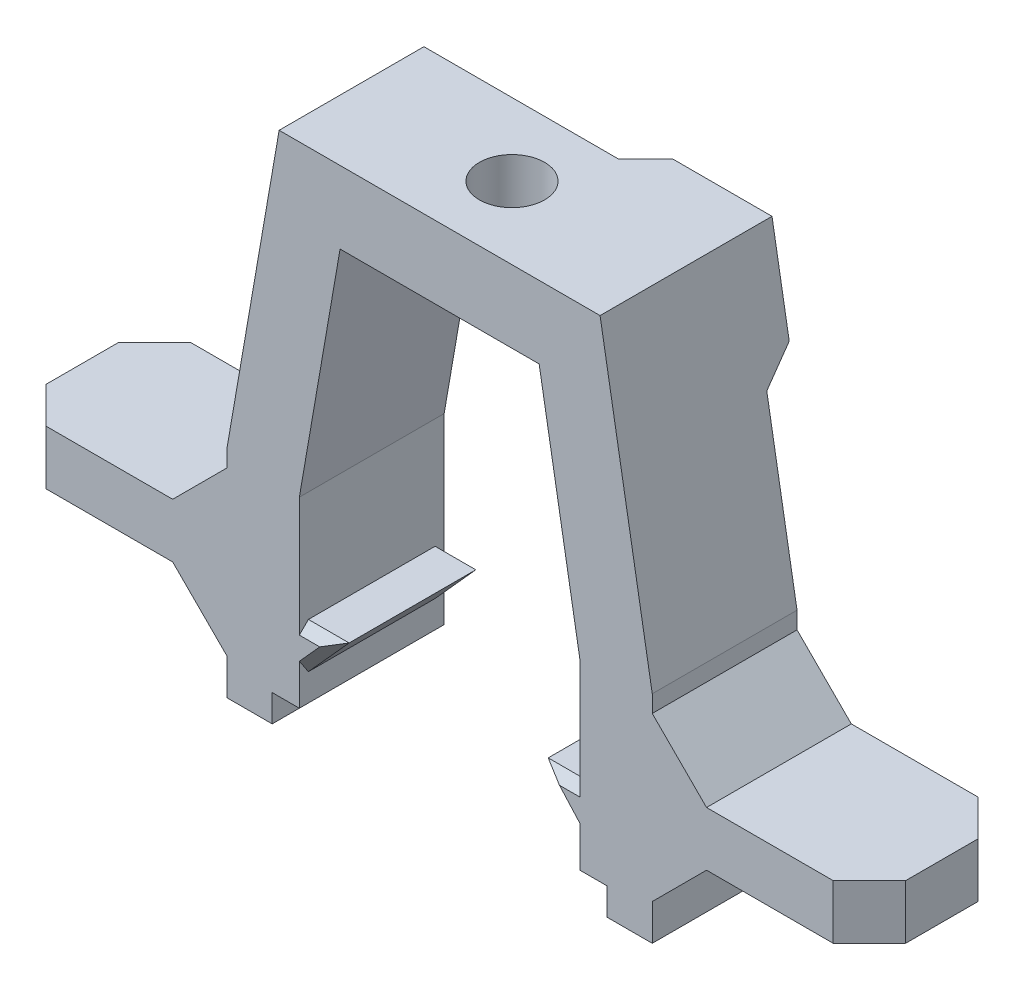
SolidWorks part; units mm, degrees
ref_plane "Front Plane" through (0, 0, 0) normal (0, 0, 1) x (1, 0, 0)
ref_plane "Top Plane" through (0, 0, 0) normal (0, 1, 0) x (1, 0, 0)
ref_plane "Right Plane" through (0, 0, 0) normal (1, 0, 0) x (0, 0, -1)
sketch "Sketch1" plane through (0, 0, 0) normal (0, 0, 1) x (1, 0, 0)
  line L0 (8.8672, 0) -> (-8.8672, 0)
  line L1 (-8.8672, 0) -> (-11.75, -16.6564)
  line L2 (-11.75, -16.6564) -> (-11.75, -28.6)
  line L3 (-11.75, -28.6) -> (-9.25, -28.6)
  line L4 (-7.75, -27.1) -> (-7.75, -25.6)
  line L5 (-7.75, -25.6) -> (-5.5, -23.1)
  line L6 (-5.5, -23.1) -> (-7.75, -23.1)
  line L7 (-7.75, -23.1) -> (-7.75, -17)
  line L8 (-7.75, -17) -> (-5.5, -4)
  line L9 (-5.5, -4) -> (5.5, -4)
  line L10 (0, 0) -> (0, -7.0392) construction
  line L11 (7.75, -17) -> (5.5, -4)
  line L12 (7.75, -23.1) -> (7.75, -17)
  line L13 (5.5, -23.1) -> (7.75, -23.1)
  line L14 (7.75, -25.6) -> (5.5, -23.1)
  line L15 (7.75, -27.1) -> (7.75, -25.6)
  line L16 (11.75, -28.6) -> (9.25, -28.6)
  line L17 (11.75, -16.6564) -> (11.75, -28.6)
  line L18 (8.8672, 0) -> (11.75, -16.6564)
  line L19 (-7.75, -27.1) -> (-9.25, -27.1)
  line L20 (-9.25, -27.1) -> (-9.25, -28.6)
  line L21 (7.75, -27.1) -> (9.25, -27.1)
  line L22 (9.25, -27.1) -> (9.25, -28.6)
  dimension "D1" = 19.1
  dimension "D5" = 4
  dimension "D2" = 2.5
  dimension "D3" = 2.25
  dimension "D4" = 4
  dimension "D8" = 3
  dimension "D6" = 11
  dimension "D7" = 13
  dimension "D9" = 15.5
  dimension "D10" = 1.5
extrude "Boss-Extrude1" add sketch "Sketch1" along normal blind 8
sketch "Sketch2" plane through (0, 0, 0) normal (0, 1, 0) x (1, 0, 0)
  line L0 (0, 0) -> (0, -8) construction
  line L1 (8.8672, 0) -> (-8.8672, 0) construction
  line L2 (8.8672, -8) -> (-8.8672, -8) construction
  line L7 (0, -6.4749) -> (0, -1.5251) construction
  line L8 (2.4749, -4) -> (-2.4749, -4) construction
  circle A0 centre (0, -4) radius 1.8
  point P1 (0, -4)
  point P8 (0, -4)
  dimension "D1" = 3.6
extrude "Cut-Extrude1" cut sketch "Sketch2" against normal through all
sketch "Sketch3" plane through (0, 0, 8) normal (0, 0, 1) x (1, 0, 0)
  line L0 (-14.75, -20.6) -> (-23.75, -20.6)
  line L1 (-23.75, -20.6) -> (-23.75, -23.6)
  line L2 (-23.75, -23.6) -> (-14.75, -23.6)
  line L3 (-14.75, -23.6) -> (-11.75, -26.6)
  line L4 (-11.75, -16.6564) -> (-11.75, -28.6) construction
  line L5 (-11.75, -26.6) -> (-11.75, -17.6)
  line L6 (-11.75, -17.6) -> (-14.75, -20.6)
  line L7 (0, 0) -> (0, -11.0245) construction
  line L8 (11.75, -17.6) -> (14.75, -20.6)
  line L9 (11.75, -26.6) -> (11.75, -17.6)
  line L10 (14.75, -23.6) -> (11.75, -26.6)
  line L11 (23.75, -23.6) -> (14.75, -23.6)
  line L12 (23.75, -20.6) -> (23.75, -23.6)
  line L13 (14.75, -20.6) -> (23.75, -20.6)
  dimension "D1" = 45
  dimension "D2" = 12
  dimension "D3" = 3
  dimension "D4" = 2
  dimension "D5" = 3
extrude "Boss-Extrude2" add sketch "Sketch3" against normal up to surface (8 mm away) up to face at (0, -20.0779, 0)
chamfer "Chamfer1" distance 2 angle 45 4 edges at (-23.75, -22.1, 0) (-23.75, -22.1, 8) (23.75, -22.1, 0) (23.75, -22.1, 8)
chamfer "Chamfer2" distance 0.5 angle 45 8 edges at (6.625, -24.35, 0) (6.625, -23.1, 0) (-6.625, -24.35, 0) (-6.625, -23.1, 0) (-6.625, -24.35, 8) (-6.625, -23.1, 8) (6.625, -24.35, 8) (6.625, -23.1, 8)
sketch "Sketch5" plane through (0, 0, 0) normal (0, 0, -1) x (-1, 0, 0)
  line L1 (-8.8672, 0) -> (8.8672, 0) construction
  line L2 (-3.8672, 0) -> (-8.8672, 0)
  line L3 (-8.8672, 0) -> (-9.7325, -5)
  line L4 (-11.75, -16.6564) -> (-8.8672, 0) construction
  line L5 (-9.7325, -5) -> (-5.6731, -5)
  line L7 (-3.8672, -4) -> (-3.8672, 0)
  line L8 (5.5, -4) -> (-5.5, -4) construction
  line L9 (-5.5, -4) -> (-7.75, -17) construction
  line L10 (-5.6731, -5) -> (-5.5, -4)
  line L11 (-5.5, -4) -> (-3.8672, -4)
  dimension "D1" = 5
  dimension "D2" = 5
extrude "Boss-Extrude3" add sketch "Sketch5" along normal blind 1.5
chamfer "Chamfer3" distance 2 angle 45 2 edges at (3.8672, -2, 0) (7.7028, -5, 0)
